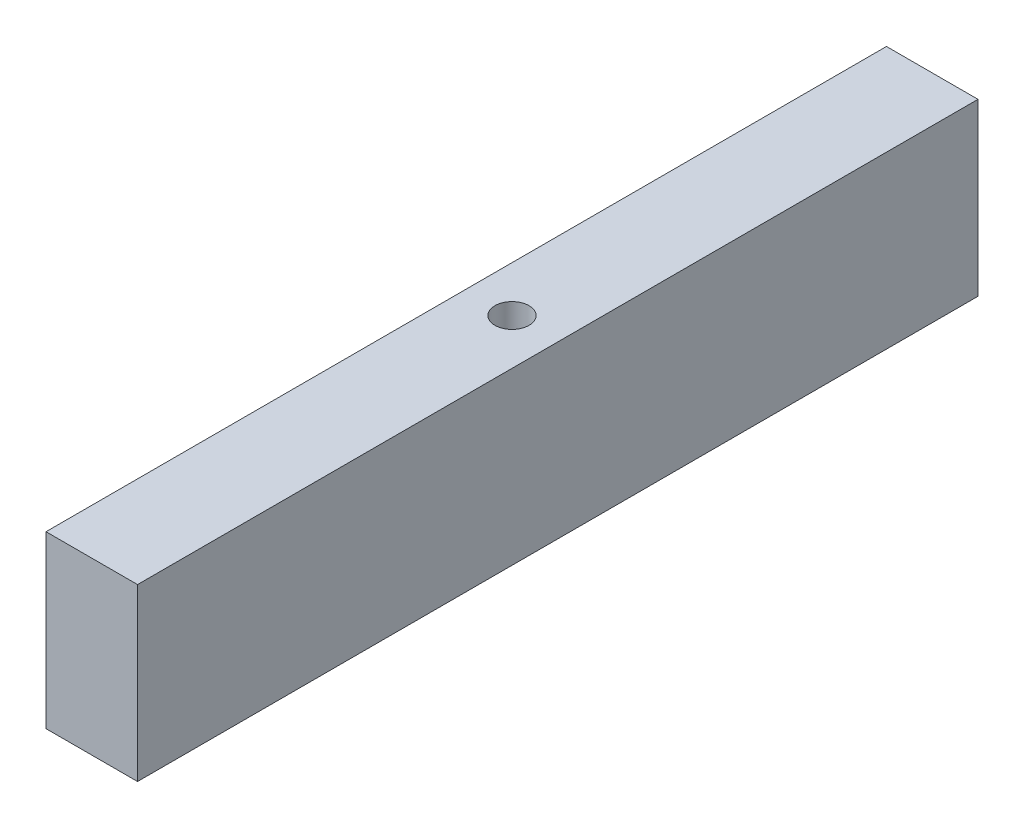
SolidWorks part; units mm, degrees
material "Gray Cast Iron"
ref_plane "Front Plane" through (0, 0, 0) normal (0, 0, 1) x (1, 0, 0)
ref_plane "Top Plane" through (0, 0, 0) normal (0, 1, 0) x (1, 0, 0)
ref_plane "Right Plane" through (0, 0, 0) normal (1, 0, 0) x (0, 0, -1)
sketch "Sketch1" plane through (0, 0, 0) normal (0, 0, 1) x (1, 0, 0)
  line L0 (-11, 0) -> (11, 0)
  line L1 (11, 0) -> (11, 41)
  line L2 (11, 41) -> (-11, 41)
  line L3 (-11, 41) -> (-11, 0)
extrude "Boss-Extrude1" add sketch "Sketch1" along normal mid plane 202
sketch "Sketch2" plane through (0, 0, 0) normal (0, 1, 0) x (1, 0, 0)
  circle A0 centre (0, 0) radius 4.1
  dimension "D1" = 8.2
extrude "Cut-Extrude1" cut sketch "Sketch2" against normal mid plane 92
